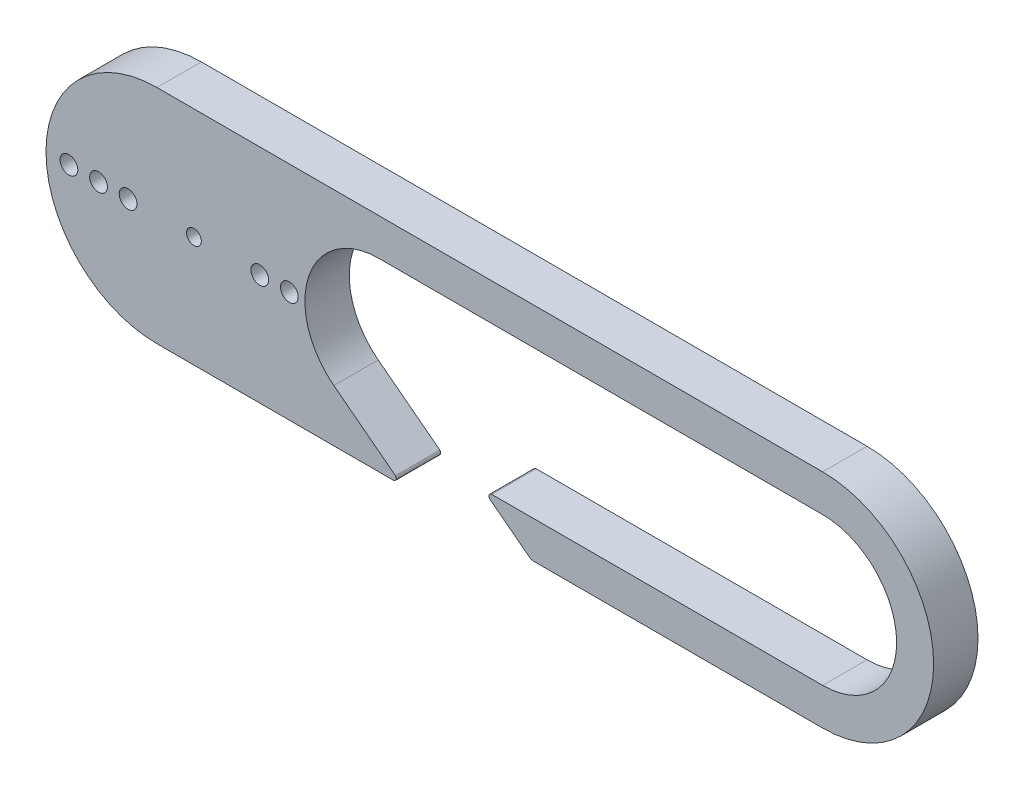
SolidWorks part; units mm, degrees
ref_plane "Front Plane" through (0, 0, 0) normal (0, 0, 1) x (1, 0, 0)
ref_plane "Top Plane" through (0, 0, 0) normal (0, 1, 0) x (1, 0, 0)
ref_plane "Right Plane" through (0, 0, 0) normal (1, 0, 0) x (0, 0, -1)
sketch "Sketch2" plane through (0, 0, 0) normal (0, 0, 1) x (1, 0, 0)
  line L0 (5.2704, 0.8557) -> (54.3236, 0.8557) construction
  line L1 (16.7704, 5.8557) -> (46.7704, 5.8557)
  line L2 (24.4073, -4.1443) -> (46.7704, -4.1443)
  line L3 (1.7704, 8.3557) -> (46.7704, 8.3557)
  line L4 (1.7704, -6.6443) -> (17.7478, -6.6443)
  line L5 (1.7704, 5.8557) -> (46.7704, 5.8557) construction
  line L6 (1.7704, -4.1443) -> (46.7704, -4.1443) construction
  line L7 (11.7704, 0.8557) -> (46.7704, 0.8557) construction
  line L8 (13.728, -3.1122) -> (17.8892, -6.3029)
  line L10 (26.9436, -6.5411) -> (24.2856, -4.5031)
  line L12 (27.2478, -6.6443) -> (46.7704, -6.6443)
  line L13 (1.7704, -6.6443) -> (46.7704, -6.6443) construction
  arc A1 (46.7704, -4.1443) -> (46.7704, 5.8557) centre (46.7704, 0.8557) ccw
  arc A2 (46.7704, -6.6443) -> (46.7704, 8.3557) centre (46.7704, 0.8557) ccw
  arc A3 (1.7704, 8.3557) -> (1.7704, -6.6443) centre (1.7704, 0.8557) ccw
  circle A4 centre (5.2704, 0.8557) radius 2.5
  arc A6 (16.7704, 5.8557) -> (13.728, -3.1122) centre (16.7704, 0.8557) ccw
  arc A7 (1.7704, 5.8557) -> (1.7704, -4.1443) centre (1.7704, 0.8557) ccw construction
  arc A8 (24.2856, -4.5031) -> (24.4073, -4.1443) centre (24.4073, -4.3443) cw
  arc A9 (27.2478, -6.6443) -> (26.9436, -6.5411) centre (27.2478, -6.1443) cw
  arc A10 (17.7478, -6.6443) -> (17.8892, -6.3029) centre (17.7478, -6.4443) ccw
  circle A11 centre (5.2704, 0.8557) radius 2.2653 construction
  arc A12 (5.1037, 3.2008) -> (5.2704, 3.1209) centre (5.2704, 3.3347) ccw
  arc A13 (5.1037, 3.2008) -> (4.7384, 3.1457) centre (4.9371, 3.0669) ccw
  arc A14 (4.6027, 3.0203) -> (4.7384, 3.1457) centre (4.5397, 3.2245) ccw
  arc A15 (5.2704, 3.1209) -> (5.437, 3.2008) centre (5.2704, 3.3347) ccw
  arc A16 (5.8024, 3.1457) -> (5.437, 3.2008) centre (5.6037, 3.0669) ccw
  arc A17 (5.8024, 3.1457) -> (5.9381, 3.0203) centre (6.0011, 3.2245) ccw
  arc A18 (5.9381, 3.0203) -> (6.1209, 3.0475) centre (6.0011, 3.2245) ccw
  arc A19 (6.4537, 2.8872) -> (6.1209, 3.0475) centre (6.2406, 2.8704) ccw
  arc A20 (6.4537, 2.8872) -> (6.5464, 2.7273) centre (6.6669, 2.9039) ccw
  arc A21 (6.5464, 2.7273) -> (6.7291, 2.6994) centre (6.6669, 2.9039) ccw
  arc A22 (7, 2.4481) -> (6.7291, 2.6994) centre (6.7914, 2.4949) ccw
  arc A23 (7, 2.4481) -> (7.0414, 2.268) centre (7.2086, 2.4013) ccw
  arc A24 (7.0414, 2.268) -> (7.2078, 2.1875) centre (7.2086, 2.4013) ccw
  arc A25 (7.3925, 1.8676) -> (7.2078, 2.1875) centre (7.207, 1.9738) ccw
  arc A26 (7.3925, 1.8676) -> (7.379, 1.6832) centre (7.578, 1.7613) ccw
  arc A27 (7.379, 1.6832) -> (7.5143, 1.5573) centre (7.578, 1.7613) ccw
  arc A28 (7.5965, 1.1971) -> (7.5143, 1.5573) centre (7.4505, 1.3533) ccw
  arc A29 (7.5965, 1.1971) -> (7.5293, 1.0249) centre (7.7425, 1.0409) ccw
  arc A30 (7.5293, 1.0249) -> (7.6214, 0.8647) centre (7.7425, 1.0409) ccw
  arc A31 (7.5938, 0.4963) -> (7.6214, 0.8647) centre (7.5004, 0.6885) ccw
  arc A32 (7.5938, 0.4963) -> (7.4788, 0.3516) centre (7.6872, 0.304) ccw
  arc A33 (7.4788, 0.3516) -> (7.5196, 0.1713) centre (7.6872, 0.304) ccw
  arc A34 (7.3846, -0.1726) -> (7.5196, 0.1713) centre (7.352, 0.0387) ccw
  arc A35 (7.3846, -0.1726) -> (7.2321, -0.277) centre (7.4173, -0.3839) ccw
  arc A36 (7.2321, -0.277) -> (7.218, -0.4612) centre (7.4173, -0.3839) ccw
  arc A37 (6.9876, -0.7501) -> (7.218, -0.4612) centre (7.0187, -0.5386) ccw
  arc A38 (6.9876, -0.7501) -> (6.8111, -0.8049) centre (6.9565, -0.9616) ccw
  arc A39 (6.8111, -0.8049) -> (6.7433, -0.9768) centre (6.9565, -0.9616) ccw
  arc A40 (6.438, -1.1849) -> (6.7433, -0.9768) centre (6.5301, -0.992) ccw
  arc A41 (6.438, -1.1849) -> (6.2532, -1.1853) centre (6.346, -1.3779) ccw
  arc A42 (6.2532, -1.1853) -> (6.1377, -1.3295) centre (6.346, -1.3779) ccw
  arc A43 (5.7847, -1.4385) -> (6.1377, -1.3295) centre (5.9295, -1.2812) ccw
  arc A44 (5.7847, -1.4385) -> (5.608, -1.3843) centre (5.6398, -1.5957) ccw
  arc A45 (5.608, -1.3843) -> (5.4551, -1.4881) centre (5.6398, -1.5957) ccw
  arc A46 (5.0856, -1.4881) -> (5.4551, -1.4881) centre (5.2704, -1.3806) ccw
  arc A47 (5.0856, -1.4881) -> (4.9328, -1.3843) centre (4.9009, -1.5957) ccw
  arc A48 (4.9328, -1.3843) -> (4.7561, -1.4385) centre (4.9009, -1.5957) ccw
  arc A49 (4.403, -1.3295) -> (4.7561, -1.4385) centre (4.6112, -1.2812) ccw
  arc A50 (4.403, -1.3295) -> (4.2875, -1.1853) centre (4.1948, -1.3779) ccw
  arc A51 (4.2875, -1.1853) -> (4.1027, -1.1849) centre (4.1948, -1.3779) ccw
  arc A52 (3.7974, -0.9768) -> (4.1027, -1.1849) centre (4.0107, -0.992) ccw
  arc A53 (3.7974, -0.9768) -> (3.7296, -0.8049) centre (3.5842, -0.9616) ccw
  arc A54 (3.7296, -0.8049) -> (3.5531, -0.7501) centre (3.5842, -0.9616) ccw
  arc A55 (3.3227, -0.4612) -> (3.5531, -0.7501) centre (3.522, -0.5386) ccw
  arc A56 (3.3227, -0.4612) -> (3.3086, -0.277) centre (3.1235, -0.3839) ccw
  arc A57 (3.3086, -0.277) -> (3.1561, -0.1726) centre (3.1235, -0.3839) ccw
  arc A58 (3.0211, 0.1713) -> (3.1561, -0.1726) centre (3.1887, 0.0387) ccw
  arc A59 (3.0211, 0.1713) -> (3.0619, 0.3516) centre (2.8535, 0.304) ccw
  arc A60 (3.0619, 0.3516) -> (2.9469, 0.4963) centre (2.8535, 0.304) ccw
  arc A61 (2.9193, 0.8647) -> (2.9469, 0.4963) centre (3.0404, 0.6885) ccw
  arc A62 (2.9193, 0.8647) -> (3.0114, 1.0249) centre (2.7983, 1.0409) ccw
  arc A63 (3.0114, 1.0249) -> (2.9442, 1.1971) centre (2.7983, 1.0409) ccw
  arc A64 (3.0265, 1.5573) -> (2.9442, 1.1971) centre (3.0902, 1.3533) ccw
  arc A65 (3.0265, 1.5573) -> (3.1617, 1.6832) centre (2.9627, 1.7613) ccw
  arc A66 (3.1617, 1.6832) -> (3.1482, 1.8676) centre (2.9627, 1.7613) ccw
  arc A67 (3.333, 2.1875) -> (3.1482, 1.8676) centre (3.3337, 1.9738) ccw
  arc A68 (3.333, 2.1875) -> (3.4993, 2.268) centre (3.3322, 2.4013) ccw
  arc A69 (3.4993, 2.268) -> (3.5408, 2.4481) centre (3.3322, 2.4013) ccw
  arc A70 (3.8116, 2.6994) -> (3.5408, 2.4481) centre (3.7493, 2.4949) ccw
  arc A71 (3.8116, 2.6994) -> (3.9943, 2.7273) centre (3.8739, 2.9039) ccw
  arc A72 (3.9943, 2.7273) -> (4.087, 2.8872) centre (3.8739, 2.9039) ccw
  arc A73 (4.4199, 3.0475) -> (4.087, 2.8872) centre (4.3001, 2.8704) ccw
  arc A74 (4.4199, 3.0475) -> (4.6027, 3.0203) centre (4.5397, 3.2245) ccw
  point P3 (25, 0)
  point P32 (5.2704, 0.8557)
  point P34 (5.2704, 0.8557)
  point P159 (5.2704, 0.8557)
  dimension "D2" = 30
  dimension "D3" = 45
  dimension "D5" = 5
  dimension "D6" = 5
  dimension "D7" = 5
  dimension "D8" = 0.2
  dimension "D9" = 0.5
  dimension "D10" = 0.2
  dimension "D1" = 2.5
  dimension "D4" = 3.5
  dimension "D11" = 9.5
  dimension "D12" = 2.2362
extrude "Boss-Extrude1" add sketch "Sketch2" along normal blind 3 contours L3 A3 L4 A2 A1 L2 L1 | A4 A73 A74 A14 A13 A12 A15 A16 A17 A18 A19 A20 A21 A22 A23 A24 A25 A26 A27 A28 A29 A30 A31 A32 A33 A34 A35 A36 A37 A38 A39 A40 A41 A42 A43 A44 A45 A46 A47 A48 A49 A50 A51 A52 A53 A54 A55 A56 A57 A58 | A74 A73 A72 A71 A70 A69 A68 A67 A66 A65 A64 A63 A62 A61 A60 A59 A58 A57 A56 A55 A54 A53 A52 A51 A50 A49 A48 A47 A46 A45 A44 A43 A42 A41 A40 A39 A38 A37 A36 A35 A34 A33 A32 A31 A30 A29 A28 A27 A26 A25 A24 region at (11.4498, 2.6607, 0) region at (2.8411, 0.8557, 0) region at (5.2704, 0.8557, 0)
sketch "Sketch3" plane through (0, 0, 3) normal (0, 0, 1) x (1, 0, 0)
  line L1 (-4.1796, 0.8557) -> (12.7204, 0.8557) construction
  line L2 (1.7704, 8.3557) -> (46.7704, 8.3557) construction
  circle A0 centre (-4.1796, 0.8557) radius 0.6
  circle A1 centre (-2.1796, 0.8557) radius 0.6
  circle A2 centre (-0.1796, 0.8557) radius 0.6
  circle A3 centre (4.2704, 0.8557) radius 0.5007
  circle A4 centre (8.7204, 0.8557) radius 0.6
  circle A5 centre (10.7204, 0.8557) radius 0.6
  circle A6 centre (12.7204, 0.8557) radius 0.6
  point P4 (0, 0)
  point P5 (0, 0)
  point P6 (0, 0)
  point P8 (0, 0)
  dimension "D1" = 2.5
  dimension "D7" = 1.2
  dimension "D8" = 1.2
  dimension "D9" = 1.2
  dimension "D10" = 1.2
  dimension "D11" = 1.2
  dimension "D12" = 1.2
  dimension "D14" = 1.0015
  dimension "D2" = 2
  dimension "D3" = 2
  dimension "D4" = 2
  dimension "D5" = 4.45
  dimension "D6" = 4.45
  dimension "D13" = 2
  dimension "D15" = 7.5
extrude "Cut-Extrude1" cut sketch "Sketch3" against normal through all both and the other way through all
